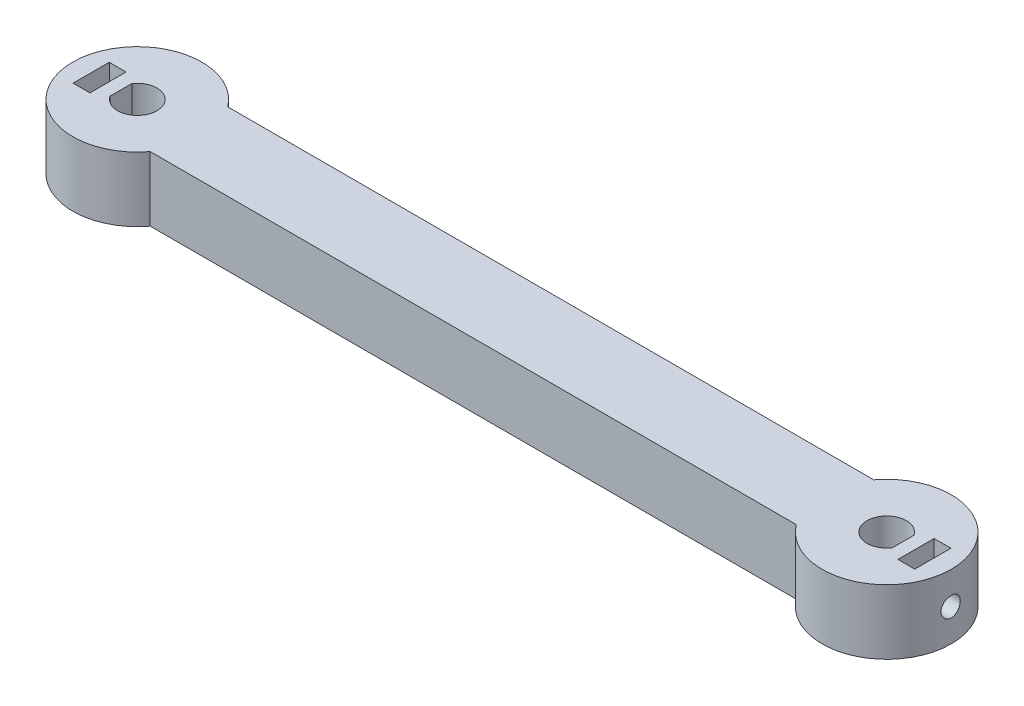
SolidWorks part; units mm, degrees
ref_plane "Plano frontal" through (0, 0, 0) normal (0, 0, 1) x (1, 0, 0)
ref_plane "Plano superior" through (0, 0, 0) normal (0, 1, 0) x (1, 0, 0)
ref_plane "Plano direito" through (0, 0, 0) normal (1, 0, 0) x (0, 0, -1)
sketch "Esboço1" plane through (0, 0, 0) normal (0, 1, 0) x (1, 0, 0)
  line L2 (8, 6) -> (108, 6)
  line L3 (8, -6) -> (108, -6)
  line L6 (-3.7598, 0) -> (4.2446, 0) construction
  line L8 (58, 14.4945) -> (58, -12.8649) construction
  arc A4 (8, 6) -> (8, -6) centre (0, 0) ccw
  arc A5 (108, -6) -> (108, 6) centre (116, 0) ccw
  dimension "D2" = 20
  dimension "D3" = 20
  dimension "D4" = 100
  dimension "D7" = 6
  dimension "D8" = 6
extrude "Ressalto-extrusão1" add sketch "Esboço1" along normal blind 10
sketch "Esboço2" plane through (0, 10, 0) normal (0, 1, 0) x (1, 0, 0)
  line L0 (-11.6519, 0) -> (19.7902, 0) construction
  line L1 (-2.5417, 1.6858) -> (-2.5417, -1.6858)
  line L2 (-2.5417, 1.6858) -> (0, 0) construction
  line L3 (0, 0) -> (-2.5417, -1.6858) construction
  line L4 (58, 11.203) -> (58, -11.7589) construction
  line L5 (118.5417, 1.6858) -> (118.5417, -1.6858)
  arc A0 (-2.5417, -1.6858) -> (-2.5417, 1.6858) centre (0, 0) ccw
  arc A1 (118.5417, -1.6858) -> (118.5417, 1.6858) centre (116, 0) cw
  dimension "D1" = 3.05
  dimension "D2" = 67.11
extrude "Corte-extrusão1" cut sketch "Esboço2" against normal up to surface (10 mm away) up to face at (58, 0, 0)
sketch "Esboço3" plane through (-2.5417, 0, 0) normal (1, 0, 0) x (0, 0, -1)
  line L0 (1.6858, 5) -> (-1.6858, 5) construction
  line L1 (1.6858, 0) -> (1.6858, 10) construction
  line L2 (-1.6858, 0) -> (-1.6858, 10) construction
  line L3 (-1.6858, 0) -> (1.6858, 0) construction
  circle A0 centre (0, 5) radius 1.5
  point P8 (0, 0)
  point P11 (0, 0)
  dimension "D1" = 3
extrude "Corte-extrusão2" cut sketch "Esboço3" against normal through all
sketch "Esboço4" plane through (118.5417, 0, 0) normal (-1, 0, 0) x (0, 0, 1)
  line L0 (-1.6858, 0) -> (1.6858, 0) construction
  line L1 (1.6858, 0) -> (1.6858, 10) construction
  circle A0 centre (0, 5) radius 1.5
  point P4 (0, 0)
  point P5 (0, 0)
  point P8 (1.6858, 5)
  dimension "D1" = 3
extrude "Corte-extrusão3" cut sketch "Esboço4" against normal through all
sketch "Esboço5" plane through (0, 10, 0) normal (0, 1, 0) x (1, 0, 0)
  line L0 (-2.5417, 1.6858) -> (-2.5417, -1.6858) construction
  line L1 (-7.1417, 2.8) -> (-4.5417, 2.8)
  line L2 (-7.1417, 2.8) -> (-7.1417, -2.8)
  line L3 (-7.1417, -2.8) -> (-4.5417, -2.8)
  line L4 (-4.5417, 2.8) -> (-4.5417, -2.8)
  line L5 (58, 11.7245) -> (58, -11.1633) construction
  line L6 (123.1417, -2.8) -> (120.5417, -2.8)
  line L7 (120.5417, 2.8) -> (120.5417, -2.8)
  line L8 (123.1417, 2.8) -> (123.1417, -2.8)
  line L9 (123.1417, 2.8) -> (120.5417, 2.8)
  point P4 (-7.1417, 0)
  dimension "D1" = 2.6
  dimension "D2" = 5.6
  dimension "D3" = 2
extrude "Corte-extrusão4" cut sketch "Esboço5" against normal blind 5
sketch "Esboço6" plane through (-2.5417, 0, 0) normal (1, 0, 0) x (0, 0, -1)
  line L0 (1.6858, 0) -> (1.6858, 10) construction
  line L1 (0, 8.2332) -> (-2.8, 6.6166)
  line L2 (-2.8, 6.6166) -> (-2.8, 3.3834)
  line L3 (-2.8, 3.3834) -> (0, 1.7668)
  line L4 (0, 1.7668) -> (2.8, 3.3834)
  line L5 (2.8, 3.3834) -> (2.8, 6.6166)
  line L6 (2.8, 6.6166) -> (0, 8.2332)
  line L7 (-1.6858, 0) -> (-1.6858, 10) construction
  circle A0 centre (0, 5) radius 2.8 construction
  point P1 (0, 0)
  point P11 (1.6858, 5)
  dimension "D1" = 5.6
extrude "Corte-extrusão5" cut sketch "Esboço6" against normal blind 2.6 from offset 2 offset against normal yes
sketch "Esboço7" plane through (118.5417, 0, 0) normal (-1, 0, 0) x (0, 0, 1)
  line L0 (1.6858, 0) -> (1.6858, 10) construction
  line L1 (0, 8.2332) -> (-2.8, 6.6166)
  line L2 (-2.8, 6.6166) -> (-2.8, 3.3834)
  line L3 (-2.8, 3.3834) -> (0, 1.7668)
  line L4 (0, 1.7668) -> (2.8, 3.3834)
  line L5 (2.8, 3.3834) -> (2.8, 6.6166)
  line L6 (2.8, 6.6166) -> (0, 8.2332)
  line L7 (-1.6858, 0) -> (-1.6858, 10) construction
  circle A0 centre (0, 5) radius 2.8 construction
  point P10 (1.6858, 5)
  dimension "D1" = 5.6
extrude "Corte-extrusão6" cut sketch "Esboço7" against normal blind 2.6 from offset 2 offset against normal yes
